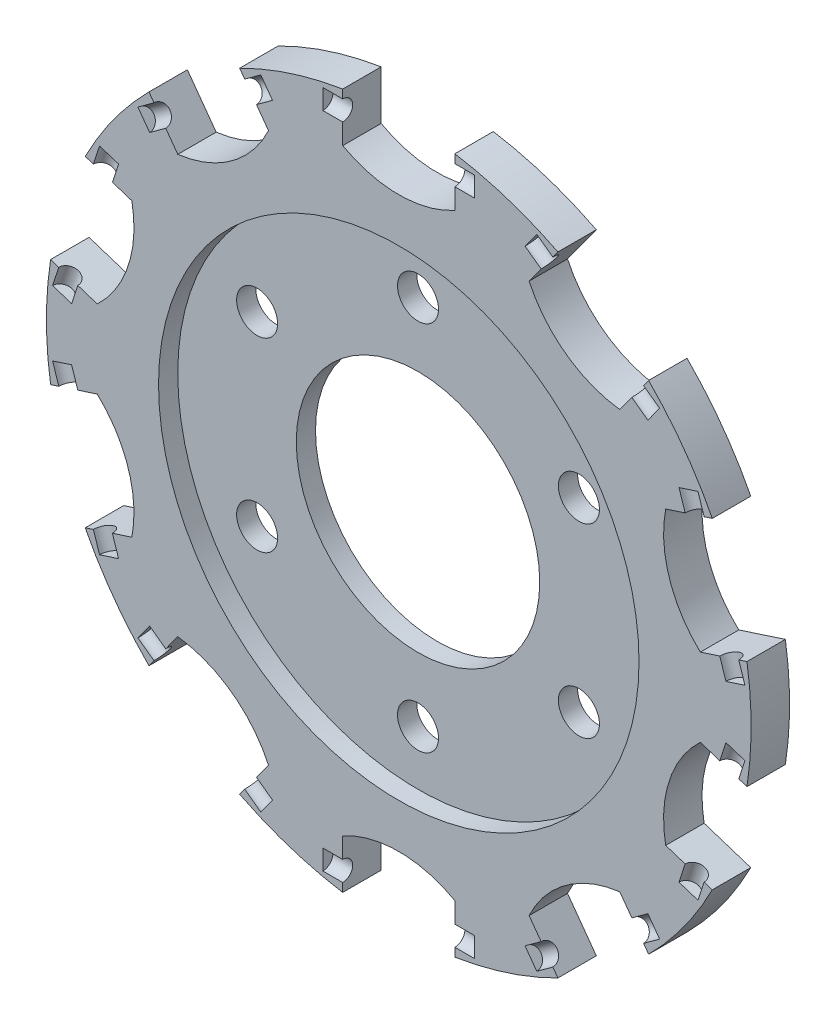
SolidWorks part; units mm, degrees
ref_plane "Front Plane" through (0, 0, 0) normal (0, 0, 1) x (1, 0, 0)
ref_plane "Top Plane" through (0, 0, 0) normal (0, 1, 0) x (1, 0, 0)
ref_plane "Right Plane" through (0, 0, 0) normal (1, 0, 0) x (0, 0, -1)
sketch "Sketch2" plane through (0, 0, 0) normal (0, 0, 1) x (1, 0, 0)
  line L2 (-4.375, 27.1498) -> (-4.375, 23.324)
  line L3 (4.375, 27.1498) -> (4.375, 23.324)
  line L4 (19.4977, 19.3931) -> (17.249, 16.298)
  line L5 (12.4188, 24.5362) -> (10.1701, 21.4411)
  line L6 (27.1729, 4.2289) -> (23.5344, 3.0466)
  line L7 (24.469, 12.5506) -> (20.8305, 11.3684)
  line L8 (24.469, -12.5506) -> (20.8305, -11.3684)
  line L9 (27.1729, -4.2289) -> (23.5344, -3.0466)
  line L10 (12.4188, -24.5362) -> (10.1701, -21.4411)
  line L11 (19.4977, -19.3931) -> (17.249, -16.298)
  line L12 (-4.375, -27.1498) -> (-4.375, -23.324)
  line L13 (4.375, -27.1498) -> (4.375, -23.324)
  line L14 (-19.4977, -19.3931) -> (-17.249, -16.298)
  line L15 (-12.4188, -24.5362) -> (-10.1701, -21.4411)
  line L16 (-27.1729, -4.2289) -> (-23.5344, -3.0466)
  line L17 (-24.469, -12.5506) -> (-20.8305, -11.3684)
  line L18 (-24.469, 12.5506) -> (-20.8305, 11.3684)
  line L19 (-27.1729, 4.2289) -> (-23.5344, 3.0466)
  line L20 (-12.4188, 24.5362) -> (-10.1701, 21.4411)
  line L21 (-19.4977, 19.3931) -> (-17.249, 16.298)
  circle A0 centre (0, 0) radius 27.5
  circle A1 centre (0, 0) radius 14.5 construction
  circle A2 centre (0, 0) radius 18.75 construction
  circle A3 centre (-12.5574, 7.25) radius 1.6
  circle A4 centre (0, 14.5) radius 1.6
  circle A5 centre (12.5574, 7.25) radius 1.6
  circle A6 centre (12.5574, -7.25) radius 1.6
  circle A7 centre (0, -14.5) radius 1.6
  circle A8 centre (-12.5574, -7.25) radius 1.6
  arc A9 (-4.375, 23.324) -> (4.375, 23.324) centre (0, 31.2162) ccw
  arc A10 (10.1701, 21.4411) -> (17.249, 16.298) centre (18.3484, 25.2544) ccw
  arc A11 (20.8305, 11.3684) -> (23.5344, 3.0466) centre (29.6883, 9.6463) ccw
  arc A12 (23.5344, -3.0466) -> (20.8305, -11.3684) centre (29.6883, -9.6463) ccw
  arc A13 (17.249, -16.298) -> (10.1701, -21.4411) centre (18.3484, -25.2544) ccw
  arc A14 (4.375, -23.324) -> (-4.375, -23.324) centre (0, -31.2162) ccw
  arc A15 (-10.1701, -21.4411) -> (-17.249, -16.298) centre (-18.3484, -25.2544) ccw
  arc A16 (-20.8305, -11.3684) -> (-23.5344, -3.0466) centre (-29.6883, -9.6463) ccw
  arc A17 (-23.5344, 3.0466) -> (-20.8305, 11.3684) centre (-29.6883, 9.6463) ccw
  arc A18 (-17.249, 16.298) -> (-10.1701, 21.4411) centre (-18.3484, 25.2544) ccw
  circle A19 centre (0, 0) radius 9.5
  circle A20 centre (0, 0) radius 18.75
  point P25 (0, 0)
  point P75 (0, 0)
  dimension "D1" = 55
  dimension "37" = 29
  dimension "D3" = 37.5
  dimension "D4" = 3.2
  dimension "D8" = 19
  dimension "D6" = 10
  dimension "D7" = 8.75
  dimension "D5" = 6
extrude "Boss-Extrude2" add sketch "Sketch2" along normal blind 3 contours A18 L21 A0 L18 A17 L19 L16 A16 L17 L14 A15 L15 L12 A14 L13 L10 A13 L11 L8 A12 L9 L6 A11 L7 L4 A10 L5 L3 A9 L2 L20 A8 A1 A3 A4 A5 A6 | A8 A1 A7 A6 A5 A4 A3 A19 region at (-5.1479, 25.2369, 0) region at (-18.2197, 0, 0)
extrude "Boss-Extrude3" add sketch "Sketch2<4>" along normal blind 3 contours A20 A8 A1 A3 A4 A5 A6 A7 region at (-18.2197, 0, 0)
sketch "Sketch2<4>" plane through (0, 0, 0) normal (0, 0, 1) x (1, 0, 0) same geometry as "Sketch2"
sketch "Sketch3" plane through (0, 0, 3) normal (0, 0, 1) x (1, 0, 0)
  line L0 (0, 28.1882) -> (0, 8.7236) construction
  line L1 (-4.375, 27.1498) -> (4.375, 27.1498) construction
  line L2 (4.375, 27.1498) -> (4.375, 23.324) construction
  line L3 (-6.683, 25.7) -> (6.8867, 25.7) construction
  line L4 (-5.925, 26.48) -> (5.925, 26.48)
  line L5 (5.925, 26.48) -> (5.925, 25.7)
  line L6 (-5.925, 26.48) -> (-5.925, 25.7)
  line L7 (5.925, 25.7) -> (-5.925, 25.7)
  arc A0 (12.4188, 24.5362) -> (4.375, 27.1498) centre (0, 0) ccw construction
  point P15 (0, 26.48)
  point P18 (5.925, 25.7)
  point P19 (-5.925, 25.7)
  point P20 (-6.683, 25.7)
  point P21 (6.8867, 25.7)
  dimension "D1" = 25.7
  dimension "D2" = 11.85
  dimension "D3" = 0.78
revolve "Cut-Revolve1" cut sketch "Sketch3" angle 360 about L7
pattern_circular "CirPattern1" count 10 every 36 about axis through (0, 0, 0) along (0, 0, 1) of "Cut-Revolve1"
sketch "Sketch4" plane through (0, 0, 3) normal (0, 0, 1) x (1, 0, 0)
  circle A0 centre (0, 0) radius 18.75
  dimension "D1" = 37.5
extrude "Cut-Extrude4" cut sketch "Sketch4" against normal blind 1.5 contours A0
